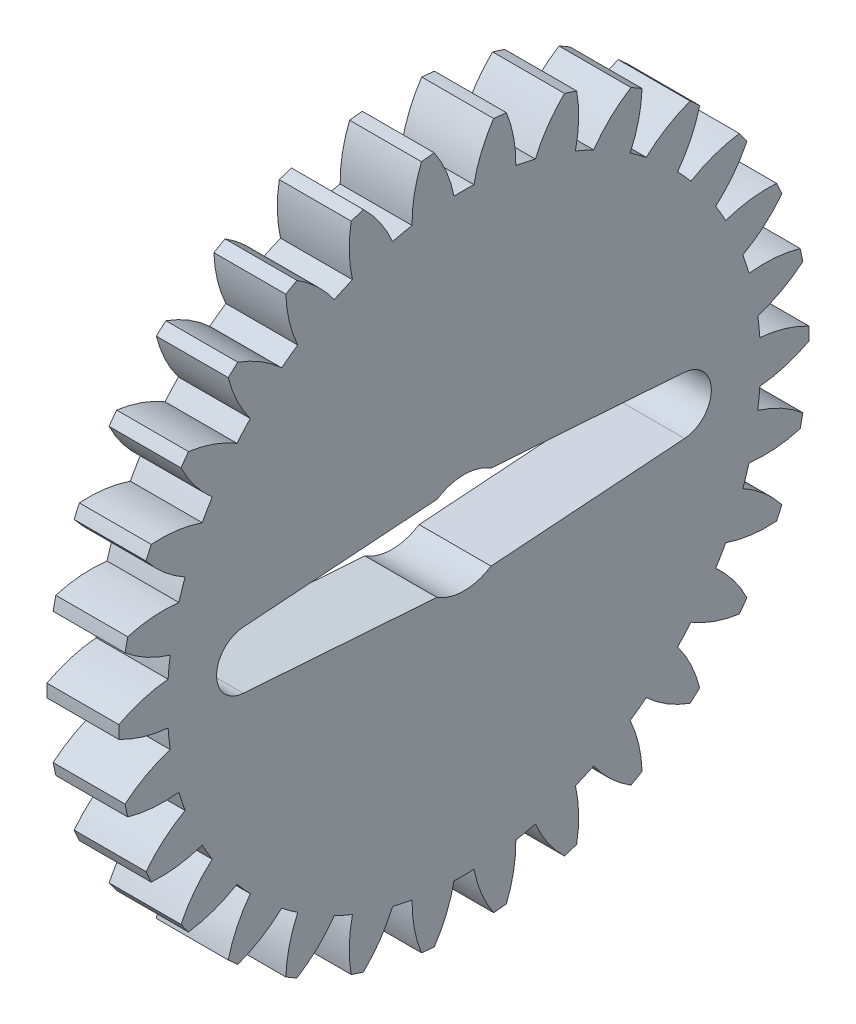
SolidWorks part; units mm, degrees
ref_plane "Plane1" through (0, 0, 0) normal (0, 0, 1) x (1, 0, 0)
ref_plane "Plane2" through (0, 0, 0) normal (0, 1, 0) x (1, 0, 0)
ref_plane "Plane3" through (0, 0, 0) normal (1, 0, 0) x (0, 0, -1)
other "Configuration Table"
sketch "HoldingSke" plane through (0, 0, 0) normal (0, 1, 0) x (1, 0, 0)
  line L0 (0, 0) -> (57.735, -33.3333)
  line L1 (-15, 0) -> (100, 0) construction
  line L2 (0, 0) -> (-2.1039, 2.3779)
  line L3 (0, 0) -> (-11.863, 4.5341)
  line L4 (0, 0) -> (7.479, 4.318)
  line L5 (0, 0) -> (-46.8476, -17.4728)
  line L6 (0, 0) -> (-4.1448, -2.7965)
  line L7 (-2.1039, 2.3779) -> (8.6587, 51.2063)
  line L8 (-76.2, 54.61) -> (-75.5, 54.61)
  line L9 (-71.009, 38.7566) -> (-53.1078, 45.2721)
  line L10 (-76.2, 71.12) -> (104.1128, 71.12)
  line L11 (0, 0) -> (-5, 0)
  line L12 (-76.2, 101.6) -> (-76.147, 101.6)
  line L13 (24.9733, 27.94) -> (52.9518, 28.4284)
  line L14 (24.9733, 27.94) -> (24.9743, 27.94)
  line L15 (24.9733, 27.94) -> (100.4006, 29.5858)
  line L16 (-63.627, -1.5) -> (-12.827, -1.5)
  circle A0 centre (0, 0) radius 2
  circle A1 centre (0, 0) radius 20.624
  circle A2 centre (0, 0) radius 37.5
  circle A3 centre (0, 0) radius 2
  dimension "MHD" = 41.248
  dimension "Hub_dia" = 75
  dimension "Bore" = 4
  dimension "MBD" = 4
  dimension "Num_teeth" = 30
  dimension "Pitch" = 66.6667
  dimension "Overall_len" = 50
  dimension "Show_teeth" = 30
  dimension "Thickness" = 5
  dimension "OAL" = 50.0005
  dimension "T_dim" = 0.7
  dimension "Ap" = 20
  dimension "H" = 19.05
  dimension "Pitch_radius" = 180.3128
  dimension "Width" = 5
  dimension "Backlash" = 0.053
  dimension "Addendum_fac" = 1
  dimension "Dedendum_fac" = 1.25
  dimension "Clearance_fac" = 0.25
  dimension "Dedendum_add" = 0.001
  dimension "Module" = 1.5
sketch "BasProSke" plane through (0, 0, 0) normal (0, 1, 0) x (1, 0, 0)
  line L0 (-10, 0) -> (60, 0) construction
  line L1 (0, 0) -> (0, 24)
  line L2 (0, 0) -> (5, 0)
  line L3 (5, 0) -> (5, 24)
  line L4 (5, 24) -> (0, 24)
  dimension "Thickness" = 5
  dimension "Diameter" = 48
revolve "Base-Revolve" add sketch "BasProSke" angle 360 about L0
sketch "TooCutSke" plane through (0, 0, 0) normal (1, 0, 0) x (0, 0, -1)
  line L1 (0, 0) -> (0, 107) construction
  line L2 (0, 0) -> (-1.2703, 22.4641) construction
  line L3 (0, 0) -> (-4.6983, 44.7014) construction
  line L4 (-1.2703, 22.4641) -> (-2.3492, 22.3507) construction
  arc A0 (0.6933, 20.6123) -> (-0.6933, 20.6123) centre (0, 0) ccw
  arc A1 (2.232, 24.1511) -> (-2.232, 24.1511) centre (0, 0) ccw
  circle A2 centre (0, 0) radius 22.5 construction
  circle A3 centre (0, 0) radius 21.1431 construction
  arc A4 (-0.6933, 20.6123) -> (-2.232, 24.1511) centre (-9.5243, 18.8764) ccw
  arc A5 (2.232, 24.1511) -> (0.6933, 20.6123) centre (9.5243, 18.8764) ccw
  dimension "Root_dia" = 41.248
  dimension "Overcut_dia" = 48.508
  dimension "Pitch_dia" = 45
  dimension "Base_dia" = 42.2862
  dimension "Flank_rad" = 9
  dimension "Half_ang" = 6
  dimension "Half_CT" = 1.0848
extrude "ToothCut" cut sketch "TooCutSke" along normal through all
fillet "Breaks" [suppressed] radius 0.03 tangent propagation no
fillet "RootFillets" [suppressed] radius 0.376
pattern_circular "TeethCuts" count 30 every 12 about axis through (-10, 0, 0) along (1, 0, 0) of "ToothCut", "RootFillets", "Breaks"
sketch "HubNeaOneSke" plane through (0, 0, 0) normal (-1, 0, 0) x (0, 0, 1)
  circle A0 centre (0, 0) radius 20.624
  dimension "Diameter" = 41.248
extrude "HubNearOne" [suppressed] add sketch "HubNeaOneSke" along normal blind 45.0005
sketch "HubNeaBotSke" plane through (0, 0, 0) normal (-1, 0, 0) x (0, 0, 1)
  circle A0 centre (0, 0) radius 20.624
  dimension "Diameter" = 41.248
extrude "HubNearBoth" [suppressed] add sketch "HubNeaBotSke" along normal blind 22.5003
ref_plane "FarPln" through (5, 0, 0) normal (1, 0, 0) x (0, 0, -1)
sketch "HubFarSke" plane through (5, 0, 0) normal (1, 0, 0) x (0, 0, -1)
  circle A0 centre (0, 0) radius 20.624
  dimension "Diameter" = 41.248
extrude "HubFar" [suppressed] add sketch "HubFarSke" along normal blind 22.5003
sketch "BorSke" plane through (0, 0, 0) normal (1, 0, 0) x (0, 0, -1)
  circle A0 centre (0, 0) radius 2
  dimension "Diameter" = 4
extrude "Bore" cut sketch "BorSke" along normal mid plane 100.001
sketch "KeySke" plane through (0, 0, 0) normal (1, 0, 0) x (0, 0, -1)
  line L0 (-0.8, 0) -> (-0.8, 2.7)
  line L1 (-0.8, 2.7) -> (0.8, 2.7)
  line L2 (0.8, 2.7) -> (0.8, 0)
  line L3 (0, 0) -> (0, 34) construction
  line L4 (-0.8, 0) -> (0.8, 0)
  dimension "Offset" = 2.7
  dimension "Width" = 1.6
extrude "Keyway" [suppressed] cut sketch "KeySke" along normal mid plane 100.001
pattern_circular "Keyway2" [suppressed] count 2 every 90 about axis through (-10, 0, 0) along (1, 0, 0) reverse direction yes
sketch "Sketch2" plane through (0, 0, 0) normal (-1, 0, 0) x (0, 0, 1)
  line L2 (0, 3.3151) -> (0, -3.3151) construction
  line L5 (-1.8835, 2.95) -> (-15.3416, 1.995)
  line L6 (-15.3416, -1.995) -> (-1.8835, -2.95)
  line L7 (15.3416, -1.995) -> (1.8835, -2.95)
  line L8 (1.8835, 2.95) -> (15.3416, 1.995)
  arc A2 (-1.8835, -2.95) -> (1.8835, -2.95) centre (0, 0) ccw
  arc A3 (-15.3416, 1.995) -> (-15.3416, -1.995) centre (-15.2, 0) ccw
  arc A5 (15.3416, 1.995) -> (15.3416, -1.995) centre (15.2, 0) cw
  arc A7 (-15.3416, -1.995) -> (-15.3416, 1.995) centre (-15.2, 0) ccw construction
  arc A8 (-1.8835, 2.95) -> (-1.8835, -2.95) centre (0, 0) ccw construction
  arc A9 (1.8835, -2.95) -> (1.8835, 2.95) centre (0, 0) ccw construction
  arc A10 (1.8835, 2.95) -> (-1.8835, 2.95) centre (0, 0) ccw
  arc A11 (15.3416, -1.995) -> (15.3416, 1.995) centre (15.2, 0) cw construction
  dimension "D1" = 7
  dimension "D2" = 4
  dimension "D3" = 5.9
  dimension "D4" = 15.2
extrude "Cut-Extrude1" cut sketch "Sketch2" against normal through all
equation "' \"Module@HoldingSke\" = 6.35"
equation "' \"Num_teeth@HoldingSke\" = 12"
equation "' \"Ap@HoldingSke\" =  20"
equation "' \"Ap@HoldingSke\" = 20"
equation "' \"Width@HoldingSke\" = 0.5 * 25.4"
equation "' \"Hub_dia@HoldingSke\"= 1 * 25.4"
equation "' \"Hub_dia@HoldingSke\" = 1 * 25.4"
equation "' \"Overall_len@HoldingSke\" = 1.0 * 25.4"
equation "' \"Bore@HoldingSke\" = 0.75 * 25.4"
equation "' \"T_dim@HoldingSke\" = 0.1 * 25.4"
equation "' \"Width@KeySke\" = 0.25 * 25.4"
equation "' \"Show_teeth@HoldingSke\" = 13"
equation "' \"Backlash@HoldingSke\" = 0.009 * 25.4"
equation "' \"Addendum_fac@HoldingSke\" = 1.0"
equation "' \"Dedendum_fac@HoldingSke\" = 1.25"
equation "' \"Dedendum_add@HoldingSke\" = 0.00005 * 25.4"
equation "' \"Clearance_fac@HoldingSke\" = 0.25"
equation "\"Pitch@HoldingSke\" = 1 / \"Module@HoldingSke\""
equation "\"Overcut_dia@TooCutSke\" = (\"Num_teeth@HoldingSke\" + 2 * \"Addendum_fac@HoldingSke\") / \"Pitch@HoldingSke\" + 0.002 * 25.4"
equation "\"Pitch_dia@TooCutSke\" = \"Num_teeth@HoldingSke\" / \"Pitch@HoldingSke\""
equation "\"Base_dia@TooCutSke\" = \"Num_teeth@HoldingSke\" / \"Pitch@HoldingSke\" * cos((\"Ap@HoldingSke\"  * 3.14159265 / 180))"
equation "\"Root_dia@TooCutSke\" = (\"Num_teeth@HoldingSke\" + 2) / \"Pitch@HoldingSke\" - 2 * (\"Addendum_fac@HoldingSke\" + \"Dedendum_fac@HoldingSke\") / \"Pitch@HoldingSke\" - \"Dedendum_add@HoldingSke\" * 2"
equation "\"Half_ang@TooCutSke\" = 180 / \"Num_teeth@HoldingSke\""
equation "\"Half_CT@TooCutSke\" = \"Num_teeth@HoldingSke\" / \"Pitch@HoldingSke\" * sin((3.14159265 / 2 / \"Num_teeth@HoldingSke\")) / 2 - 7 * \"Backlash@HoldingSke\" / 4"
equation "\"Flank_rad@TooCutSke\" = \"Num_teeth@HoldingSke\" / \"Pitch@HoldingSke\" / 5"
equation "\"Radius@RootFillets\" = \"Clearance_fac@HoldingSke\" / \"Pitch@HoldingSke\" + \"Dedendum_add@HoldingSke\""
equation "\"Break_rad@Breaks\" = 0.02 / \"Pitch@HoldingSke\""
equation "\"Thickness@HoldingSke\" = \"Width@HoldingSke\""
equation "\"OAL@HoldingSke\" = \"Thickness@HoldingSke\""
equation "\"MHD@HoldingSke\" = (\"Num_teeth@HoldingSke\" + 2) / \"Pitch@HoldingSke\" - 2 * (\"Addendum_fac@HoldingSke\" + \"Dedendum_fac@HoldingSke\")  / \"Pitch@HoldingSke\" - \"Dedendum_add@HoldingSke\" * 2"
equation "\"MBD@HoldingSke\" = (\"Num_teeth@HoldingSke\" + 2) / \"Pitch@HoldingSke\" - 2 * (\"Addendum_fac@HoldingSke\" + \"Dedendum_fac@HoldingSke\")  / \"Pitch@HoldingSke\" - \"Dedendum_add@HoldingSke\" * 2 - 0.002 * 25.4"
equation "\"MHD@HoldingSke\" = ((sgn( \"MHD@HoldingSke\" - \"Hub_dia@HoldingSke\" )-1)*( \"MHD@HoldingSke\" - \"Hub_dia@HoldingSke\" ))/-2+ \"Hub_dia@HoldingSke\""
equation "\"MBD@HoldingSke\" = ((sgn( \"MBD@HoldingSke\" - \"Bore@HoldingSke\" )-1)*( \"MBD@HoldingSke\" - \"Bore@HoldingSke\" ))/-2+ \"Bore@HoldingSke\""
equation "\"OAL@HoldingSke\" = ((sgn( \"OAL@HoldingSke\" - \"Overall_len@HoldingSke\" )+1)*( \"OAL@HoldingSke\" - \"Overall_len@HoldingSke\" ))/2 + \"Overall_len@HoldingSke\" + 0.000002 * 25.4"
equation "\"Num_teeth@TeethCuts\" = int( \"Show_teeth@HoldingSke\" ) + 1"
equation "\"Num_teeth@TeethCuts\" = ((sgn( \"Num_teeth@TeethCuts\" - \"Num_teeth@HoldingSke\" )-1)*( \"Num_teeth@TeethCuts\" - \"Num_teeth@HoldingSke\" ))/-2+ \"Num_teeth@HoldingSke\""
equation "\"Num_teeth@TeethCuts\" = ((sgn( \"Num_teeth@TeethCuts\" - 2.0)+1)*( \"Num_teeth@TeethCuts\" - 2.0))/2 +2.0"
equation "\"Angle@TeethCuts\" = 360.0 / \"Num_teeth@HoldingSke\""
equation "\"Diameter@BasProSke\" = (\"Num_teeth@HoldingSke\" + 2 * \"Addendum_fac@HoldingSke\") / \"Pitch@HoldingSke\""
equation "\"Thickness@BasProSke\"  = \"Thickness@HoldingSke\""
equation "' \"Fillet_rad@BasProSke\" =  \"Thickness@HoldingSke\" * 0.05"
equation "' \"Fillet_rad@BasProSke\" = \"Thickness@HoldingSke\" * 0.05"
equation "\"MHD@HoldingSke\" = ((sgn( \"MHD@HoldingSke\" - \"Root_dia@TooCutSke\" )-1)*( \"MHD@HoldingSke\" - \"Root_dia@TooCutSke\" ))/-2+ \"Root_dia@TooCutSke\""
equation "\"Diameter@HubNeaOneSke\" = \"MHD@HoldingSke\""
equation "\"Length@HubNearOne\" = \"OAL@HoldingSke\" - \"Thickness@BasProSke\""
equation "\"Diameter@HubNeaBotSke\" = \"MHD@HoldingSke\""
equation "\"Length@HubNearBoth\" = ( \"OAL@HoldingSke\" - \"Thickness@BasProSke\" ) / 2.0"
equation "\"Thickness@FarPln\" = \"Thickness@BasProSke\""
equation "\"Diameter@HubFarSke\" = \"MHD@HoldingSke\""
equation "\"Length@HubFar\" = ( \"OAL@HoldingSke\" - \"Thickness@BasProSke\" ) / 2.0"
equation "\"Diameter@BorSke\" = \"MBD@HoldingSke\""
equation "\"D1@Bore\" = \"OAL@HoldingSke\" * 2.0"
equation "\"D1@Keyway\" = \"OAL@HoldingSke\" * 2.0"
equation "\"Offset@KeySke\" = \"T_dim@HoldingSke\" + \"MBD@HoldingSke\" / 2.0"
